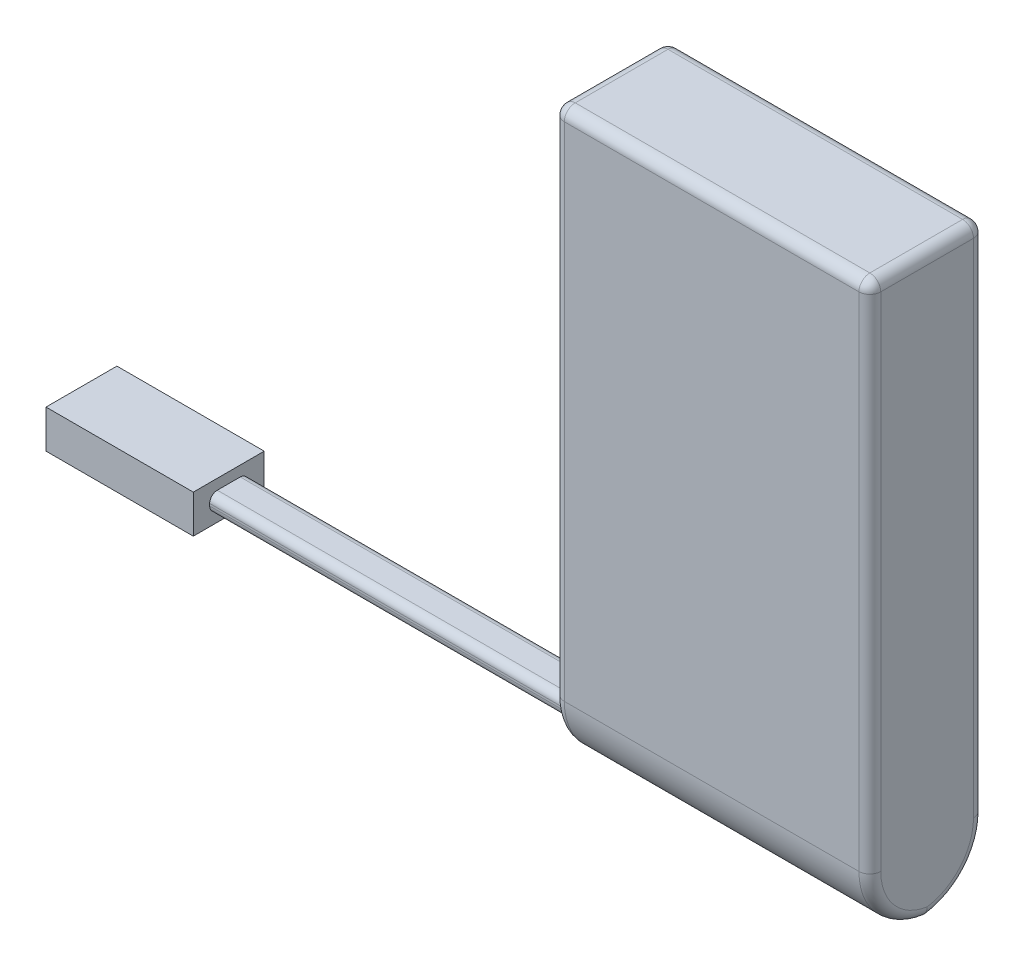
SolidWorks part; units mm, degrees
ref_plane "Alzado" through (0, 0, 0) normal (1, 0, 0) x (0, 1, 0)
ref_plane "Planta" through (0, 0, 0) normal (0, 0, 1) x (0, 1, 0)
ref_plane "Vista lateral" through (0, 0, 0) normal (0, 1, 0) x (-1, 0, 0)
sketch "Croquis1" plane through (0, 0, 0) normal (0, 0, 1) x (0, 1, 0)
  line L1 (-26.5, 14.5) -> (26.5, 14.5)
  line L2 (-26.5, 14.5) -> (-26.5, -14.5)
  line L3 (-26.5, -14.5) -> (26.5, -14.5)
  line L4 (26.5, 14.5) -> (26.5, -14.5)
  line L5 (-26.5, 14.5) -> (26.5, -14.5) construction
  line L6 (-26.5, -14.5) -> (26.5, 14.5) construction
  point P0 (0, 0)
  dimension "D1" = 53
  dimension "D2" = 29
extrude "Saliente-Extruir1" add sketch "Croquis1" along normal blind 10.5
fillet "Redondeo1" radius 6 2 edges at (0, -26.5, 0) (0, -26.5, 10.5)
fillet "Redondeo2" radius 1 12 edges at (-14.5, -24.4686, 1.5) (-14.5, -24.4686, 9) (14.5, -24.4686, 1.5) (14.5, -24.4686, 9) (-14.5, 3, 0) (-14.5, 3, 10.5) (-14.5, 26.5, 5.25) (0, 26.5, 0) (0, 26.5, 10.5) (14.5, 26.5, 5.25) (14.5, 3, 0) (14.5, 3, 10.5)
sketch "Croquis2" plane through (-14.5, 0, 0) normal (-1, 0, 0) x (0, -1, 0)
  line L1 (24.5434, 7) -> (24.7434, 7)
  line L2 (23.8434, 6.3) -> (23.8434, 4.2)
  line L3 (24.5434, 3.5) -> (24.7434, 3.5)
  line L4 (25.4434, 6.3) -> (25.4434, 4.2)
  line L5 (23.8434, 7) -> (25.4434, 3.5) construction
  line L6 (23.8434, 3.5) -> (25.4434, 7) construction
  arc A1 (24.7434, 3.5) -> (25.4434, 4.2) centre (24.7434, 4.2) ccw
  arc A2 (23.8434, 4.2) -> (24.5434, 3.5) centre (24.5434, 4.2) ccw
  arc A3 (24.5434, 7) -> (23.8434, 6.3) centre (24.5434, 6.3) ccw
  arc A4 (24.7434, 7) -> (25.4434, 6.3) centre (24.7434, 6.3) cw
  point P0 (24.6434, 5.25)
  point P8 (25.4434, 5.25)
  dimension "D1" = 3.5
  dimension "D3" = 0.7
  dimension "D2" = 1.6
extrude "Saliente-Extruir2" add sketch "Croquis2" along normal blind 35
sketch "Croquis3" plane through (-49.5, 0, 0) normal (-1, 0, 0) x (0, -1, 0)
  line L0 (24.7434, 7) -> (24.5434, 7) construction
  line L1 (22.8934, 8.5) -> (26.3934, 8.5)
  line L2 (22.8934, 8.5) -> (22.8934, 2)
  line L3 (22.8934, 2) -> (26.3934, 2)
  line L4 (26.3934, 8.5) -> (26.3934, 2)
  line L5 (22.8934, 8.5) -> (26.3934, 2) construction
  line L6 (22.8934, 2) -> (26.3934, 8.5) construction
  point P0 (24.6434, 5.25)
  point P8 (24.6434, 7)
  dimension "D1" = 6.5
  dimension "D2" = 3.5
extrude "Saliente-Extruir3" add sketch "Croquis3" along normal blind 13.5
